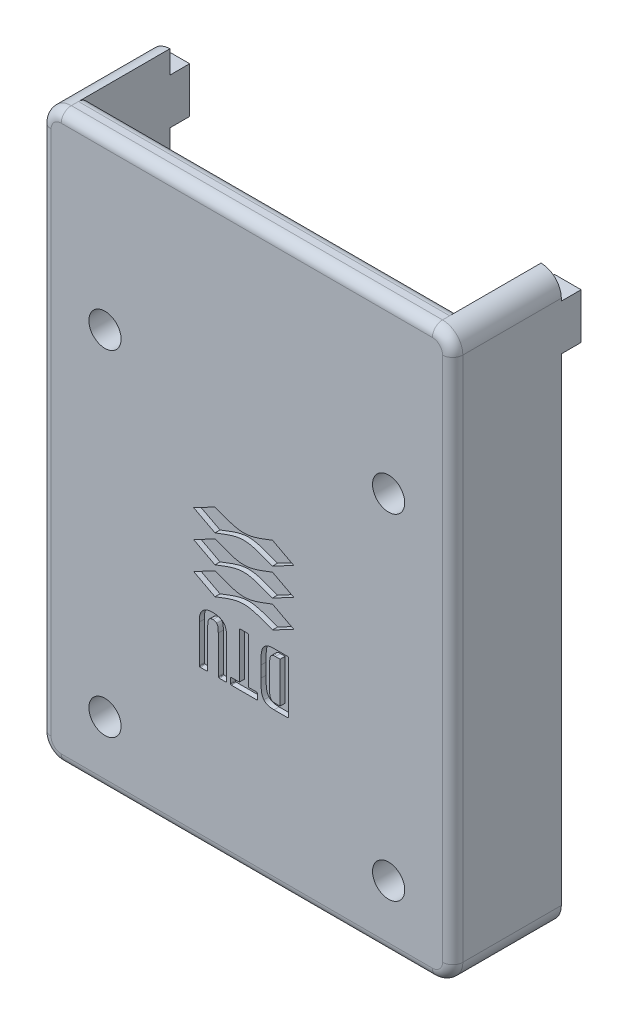
SolidWorks part; units mm, degrees
ref_plane "Front Plane" through (0, 0, 0) normal (0, 0, 1) x (1, 0, 0)
ref_plane "Top Plane" through (0, 0, 0) normal (0, 1, 0) x (1, 0, 0)
ref_plane "Right Plane" through (0, 0, 0) normal (1, 0, 0) x (0, 0, -1)
sketch "Sketch1" plane through (0, 0, 0) normal (0, 0, 1) x (1, 0, 0)
  line L1 (-7.3177, 20.9633) -> (28.2423, 20.9633)
  line L2 (-7.3177, 20.9633) -> (-7.3177, -29.8367)
  line L3 (-7.3177, -29.8367) -> (28.2423, -29.8367)
  line L4 (28.2423, 20.9633) -> (28.2423, -29.8367)
  line L5 (-7.8177, 21.4633) -> (28.7423, 21.4633)
  line L6 (-7.8177, 21.4633) -> (-7.8177, -30.3367)
  line L7 (-7.8177, -30.3367) -> (28.7423, -30.3367)
  line L8 (28.7423, 21.4633) -> (28.7423, -30.3367)
  line L9 (-9.8177, 23.4633) -> (30.7423, 23.4633)
  line L10 (-9.8177, 23.4633) -> (-9.8177, -32.3367)
  line L11 (-9.8177, -32.3367) -> (30.7423, -32.3367)
  line L12 (30.7423, 23.4633) -> (30.7423, -32.3367)
  circle A0 centre (-3.5077, 6.9933) radius 1.5875
  circle A1 centre (24.4323, 6.9933) radius 1.5875
  circle A2 centre (-3.5077, -26.0267) radius 1.5875
  circle A3 centre (24.4323, -26.0267) radius 1.5875
  dimension "D3" = 3.175
  dimension "D4" = 3.175
  dimension "D5" = 3.175
  dimension "D6" = 3.175
  dimension "D1" = 50.8
  dimension "D2" = 35.56
  dimension "D7" = 3.81
  dimension "D8" = 3.81
  dimension "D9" = 3.81
  dimension "D10" = 3.81
  dimension "D11" = 27.94
  dimension "D12" = 33.02
  dimension "D13" = 27.94
  dimension "D14" = 3.81
  dimension "D15" = 0.5
  dimension "D16" = 0.5
  dimension "D17" = 0.5
  dimension "D18" = 0.5
  dimension "D19" = 2
  dimension "D20" = 2
  dimension "D21" = 2
  dimension "D22" = 2
extrude "Boss-Extrude1" add sketch "Sketch1" along normal blind 10.7 contours A1 | A3 | A2 | L9 L12 L11 L10 | A0 region at (24.4323, 6.9933, 0) region at (-3.5077, -26.0267, 0) region at (24.4323, -26.0267, 0)
extrude "Cut-Extrude1" cut sketch "Sketch1<6>" along normal blind 8.7 contours L6 L7 L8 L5
sketch "Sketch1<6>" plane through (0, 0, 0) normal (0, 0, 1) x (1, 0, 0) same geometry as "Sketch1"
sketch "Sketch3" plane through (0, -32.3367, 0) normal (0, -1, 0) x (1, 0, 0)
  line L0 (-9.8177, 0) -> (30.7423, 0) construction
  line L1 (4.1823, 0) -> (16.7423, 0)
  line L2 (4.1823, 0) -> (4.1823, 8)
  line L3 (4.1823, 8) -> (16.7423, 8)
  line L4 (16.7423, 0) -> (16.7423, 8)
  line L5 (30.7423, 10.7) -> (30.7423, 0) construction
  line L6 (-9.8177, 10.7) -> (-9.8177, 0) construction
  dimension "D1" = 8
  dimension "D2" = 14
  dimension "D3" = 14
  dimension "D4" = 12.56
extrude "Cut-Extrude2" cut sketch "Sketch3" against normal blind 5
sketch "Sketch4" plane through (0, 23.4633, 0) normal (0, 1, 0) x (1, 0, 0)
  line L0 (-9.8177, 0) -> (30.7423, 0) construction
  line L1 (-7.8177, 0) -> (28.7423, 0)
  line L2 (-7.8177, 0) -> (-7.8177, -8)
  line L3 (-7.8177, -8) -> (28.7423, -8)
  line L4 (28.7423, 0) -> (28.7423, -8)
  line L5 (-9.8177, -10.7) -> (-9.8177, 0) construction
  line L6 (30.7423, -10.7) -> (30.7423, 0) construction
  dimension "D1" = 8
  dimension "D2" = 2
  dimension "D3" = 2
extrude "Cut-Extrude3" cut sketch "Sketch4" against normal blind 5
sketch "Sketch5" plane through (0, 0, 8.7) normal (0, 0, -1) x (-1, 0, 0)
  line L0 (-24.4323, 9.9933) -> (-28.7423, 9.9933)
  line L1 (-28.7423, 21.4633) -> (-28.7423, -30.3367) construction
  line L2 (-28.7423, 9.9933) -> (-28.7423, 3.9933)
  line L3 (-28.7423, 3.9933) -> (-24.4323, 3.9933)
  line L4 (3.5077, 9.9933) -> (7.8177, 9.9933)
  line L5 (7.8177, 21.4633) -> (7.8177, -30.3367) construction
  line L6 (7.8177, 9.9933) -> (7.8177, 3.9933)
  line L7 (7.8177, 3.9933) -> (3.5077, 3.9933)
  line L8 (3.5077, -22.7267) -> (7.8177, -22.7267)
  line L9 (7.8177, -22.7267) -> (7.8177, -29.3267)
  line L10 (7.8177, 23.4633) -> (7.8177, -30.3367) construction
  line L11 (7.8177, -29.3267) -> (3.5077, -29.3267)
  line L12 (-24.4323, -22.7267) -> (-28.7423, -22.7267)
  line L13 (-28.7423, 23.4633) -> (-28.7423, -30.3367) construction
  line L14 (-28.7423, -22.7267) -> (-28.7423, -29.3267)
  line L15 (-28.7423, -29.3267) -> (-24.4323, -29.3267)
  circle A0 centre (-24.4323, 6.9933) radius 3
  circle A1 centre (3.5077, 6.9933) radius 3
  circle A2 centre (3.5077, -26.0267) radius 3.3
  circle A3 centre (-24.4323, -26.0267) radius 3.3
  circle M2 centre (-24.4323, 6.9933) radius 1.5875
  circle M3 centre (-24.4323, -26.0267) radius 1.5875
  circle M4 centre (3.5077, -26.0267) radius 1.5875
  circle M5 centre (3.5077, 6.9933) radius 1.5875
  line M7 (-28.7423, 21.4633) -> (-28.7423, -30.3367)
  line M9 (7.8177, -30.3367) -> (7.8177, 21.4633)
  dimension "D1" = 6
extrude "Boss-Extrude3" add sketch "Sketch5" along normal blind 8 contours A0 M2 | A1 M5 | A2 M4 | A3 M3 region at (22.371, 9.0546, 8.7) region at (-5.569, 9.0546, 8.7) region at (-5.7752, -23.7593, 8.7) region at (22.1648, -23.7593, 8.7)
extrude "Boss-Extrude4" add sketch "Sketch5<5>" along normal blind 8 contours A0 L0 L3 M7 | A1 L7 L4 M9 | A2 L11 L8 M9 | A3 L12 L15 M7 region at (27.6507, 6.9933, 8.7) region at (26.5873, -22.8056, 8.7) region at (-7.7389, -26.0267, 8.7) region at (-6.7261, 6.9933, 8.7)
sketch "Sketch5<5>" plane through (0, 0, 8.7) normal (0, 0, -1) x (-1, 0, 0) same geometry as "Sketch5"
fillet "Fillet1" radius 2 8 edges at (-9.8177, 23.4633, 5.35) (30.7423, 23.4633, 5.35) (-9.8177, -32.3367, 5.35) (30.7423, -32.3367, 5.35) (4.1823, -31.3367, 0) (16.7423, -31.3367, 0) (16.7423, -31.3367, 8) (4.1823, -31.3367, 8)
fillet "Fillet2" radius 1 9 edges at (-9.2319, 22.8775, 10.7) (-9.8177, -4.4367, 10.7) (-9.2319, -31.7509, 10.7) (10.4623, -32.3367, 10.7) (30.1565, -31.7509, 10.7) (30.7423, -4.4367, 10.7) (30.1565, 22.8775, 10.7) (10.4623, 23.4633, 10.7) (10.4623, 23.4633, 8)
sketch "Sketch6" plane through (0, 0, 0) normal (0, 0, -1) x (-1, 0, 0)
  line L0 (-30.7423, 21.4633) -> (-30.7423, -30.3367) construction
  line L1 (-28.1423, 21.2133) -> (-30.7423, 21.2133)
  line L2 (-28.1423, 21.2133) -> (-28.1423, 16.7133)
  line L3 (-28.1423, 16.7133) -> (-30.7423, 16.7133)
  line L4 (-30.7423, 21.2133) -> (-30.7423, 16.7133)
  line L5 (9.8177, 21.4633) -> (9.8177, -30.3367) construction
  line L6 (7.8177, 21.2133) -> (9.8177, 21.2133)
  line L7 (7.8177, 21.2133) -> (7.8177, 16.7133)
  line L8 (7.8177, 16.7133) -> (9.8177, 16.7133)
  line L9 (9.8177, 21.2133) -> (9.8177, 16.7133)
  line L12 (7.8177, 23.4633) -> (-28.7423, 23.4633) construction
  dimension "D1" = 4.5
  dimension "D2" = 4.5
  dimension "D3" = 2.25
  dimension "D4" = 2.25
extrude "Boss-Extrude5" add sketch "Sketch6" along normal blind 1.95
sketch "Sketch7" plane through (31.1286, 28.3579, 10.7) normal (0, 0, -1) x (1, 0, 0)
  line L0 (-23.8027, 38.7188) -> (-25.9021, 37.616)
  line L1 (-16.0371, 37.616) -> (-18.136, 38.7188)
  line L2 (-18.136, 36.5147) -> (-16.0371, 37.616)
  line L3 (-25.9021, 37.616) -> (-23.8027, 36.5147)
  line L4 (-23.8027, 35.9943) -> (-25.9021, 34.8925)
  line L5 (-16.0371, 34.8925) -> (-18.136, 35.9943)
  line L6 (-18.136, 33.7901) -> (-16.0371, 34.8925)
  line L7 (-25.9021, 34.8925) -> (-23.8027, 33.7901)
  line L8 (-23.8027, 33.2702) -> (-25.9021, 32.1684)
  line L9 (-16.0371, 32.1684) -> (-18.136, 33.2702)
  line L10 (-18.136, 31.0666) -> (-16.0371, 32.1684)
  line L11 (-25.9021, 32.1684) -> (-23.8027, 31.0666)
  line L12 (-17.9818, 45.4573) -> (-16.6721, 45.4573)
  line L13 (-19.2753, 42.2828) -> (-19.2753, 43.4059)
  line L14 (-16.6721, 40.2314) -> (-17.9818, 40.2314)
  line L15 (-16.5624, 45.3476) -> (-16.5624, 40.3411)
  line L16 (-17.3934, 40.8426) -> (-17.3934, 44.8466)
  line L17 (-17.8553, 40.8426) -> (-17.3934, 40.8426)
  line L18 (-18.433, 43.4635) -> (-18.433, 42.2252)
  line L19 (-17.3934, 44.8466) -> (-17.8553, 44.8466)
  line L20 (-25.348, 41.6503) -> (-25.348, 45.3476)
  line L21 (-22.6453, 45.3476) -> (-22.6453, 41.6503)
  line L22 (-23.3666, 45.4573) -> (-22.7549, 45.4573)
  line L23 (-23.4767, 41.6512) -> (-23.4767, 45.3476)
  line L24 (-24.5166, 45.3476) -> (-24.5166, 41.6512)
  line L25 (-25.2384, 45.4573) -> (-24.6262, 45.4573)
  line L26 (-21.3961, 44.797) -> (-21.3961, 40.3411)
  line L27 (-22.1824, 44.797) -> (-21.3961, 44.797)
  line L28 (-22.2923, 45.3476) -> (-22.2923, 44.9066)
  line L29 (-19.7213, 45.4573) -> (-22.1824, 45.4573)
  line L30 (-19.6112, 44.9066) -> (-19.6112, 45.3476)
  line L31 (-20.5074, 44.797) -> (-19.7213, 44.797)
  line L32 (-20.5074, 40.3411) -> (-20.5074, 44.797)
  line L33 (-21.287, 40.2314) -> (-20.617, 40.2314)
  spline S0 degree 3 poles (-18.136, 38.7188) (-20.8551, 37.6612) (-21.0846, 37.6612) (-23.8027, 38.7188) knots 4 4 4 4 5 5 5 5
  spline S1 degree 3 poles (-23.8027, 36.5147) (-21.0846, 37.5719) (-20.8551, 37.5719) (-18.136, 36.5147) knots 1 1 1 1 2 2 2 2
  spline S2 degree 3 poles (-18.136, 35.9943) (-20.8551, 34.9371) (-21.0846, 34.9371) (-23.8027, 35.9943) knots 4 4 4 4 5 5 5 5
  spline S3 degree 3 poles (-23.8027, 33.7901) (-21.0846, 34.8478) (-20.8551, 34.8478) (-18.136, 33.7901) knots 1 1 1 1 2 2 2 2
  spline S4 degree 3 poles (-18.136, 33.2702) (-20.8551, 32.2126) (-21.0846, 32.2126) (-23.8027, 33.2702) knots 4 4 4 4 5 5 5 5
  spline S5 degree 3 poles (-23.8027, 31.0666) (-21.0846, 32.1238) (-20.8551, 32.1238) (-18.136, 31.0666) knots 1 1 1 1 2 2 2 2
  spline S6 degree 3 poles (-18.9888, 45.0981) (-18.8008, 45.3417) (-18.4905, 45.4573) (-17.9818, 45.4573) knots 10 10 10 10 11 11 11 11
  spline S7 degree 3 poles (-19.2753, 43.4059) (-19.2753, 44.229) (-19.2664, 44.7657) (-18.9888, 45.0981) knots 9 9 9 9 10 10 10 10
  spline S8 degree 3 poles (-18.9888, 40.5906) (-19.2664, 40.923) (-19.2753, 41.4598) (-19.2753, 42.2828) knots 7 7 7 7 8 8 8 8
  spline S9 degree 3 poles (-17.9818, 40.2314) (-18.4905, 40.2314) (-18.8008, 40.347) (-18.9888, 40.5906) knots 6 6 6 6 7 7 7 7
  spline S10 degree 3 poles (-16.5912, 40.2607) (-16.6088, 40.2433) (-16.6329, 40.2314) (-16.6721, 40.2314) knots 4 4 4 4 5 5 5 5
  spline S11 degree 3 poles (-16.5624, 40.3411) (-16.5624, 40.3019) (-16.5738, 40.2781) (-16.5912, 40.2607) knots 3 3 3 3 4 4 4 4
  spline S12 degree 3 poles (-16.5912, 45.4285) (-16.5738, 45.4106) (-16.5624, 45.3873) (-16.5624, 45.3476) knots 1 1 1 1 2 2 2 2
  spline S13 degree 3 poles (-16.6721, 45.4573) (-16.6329, 45.4573) (-16.6088, 45.4454) (-16.5912, 45.4285) knots 0 0 0 0 1 1 1 1
  spline S14 degree 3 poles (-18.2752, 40.9885) (-18.1809, 40.8754) (-18.0591, 40.8426) (-17.8553, 40.8426) knots 5 5 5 5 6 6 6 6
  spline S15 degree 3 poles (-18.433, 42.2252) (-18.433, 41.5153) (-18.4206, 41.1631) (-18.2752, 40.9885) knots 4 4 4 4 5 5 5 5
  spline S16 degree 3 poles (-18.2752, 44.7002) (-18.4206, 44.5256) (-18.433, 44.1734) (-18.433, 43.4635) knots 2 2 2 2 3 3 3 3
  spline S17 degree 3 poles (-17.8553, 44.8466) (-18.0591, 44.8466) (-18.1809, 44.8134) (-18.2752, 44.7002) knots 1 1 1 1 2 2 2 2
  spline S18 degree 3 poles (-25.0491, 40.54) (-25.2887, 40.8183) (-25.348, 41.1507) (-25.348, 41.6503) knots 20 20 20 20 21 21 21 21
  spline S19 degree 3 poles (-23.9991, 40.1654) (-24.5138, 40.1654) (-24.8452, 40.3034) (-25.0491, 40.54) knots 19 19 19 19 20 20 20 20
  spline S20 degree 3 poles (-22.9323, 40.5395) (-23.1543, 40.2949) (-23.4904, 40.1654) (-23.9991, 40.1654) knots 18 18 18 18 19 19 19 19
  spline S21 degree 3 poles (-22.6453, 41.6503) (-22.6453, 41.112) (-22.7185, 40.7747) (-22.9323, 40.5395) knots 17 17 17 17 18 18 18 18
  spline S22 degree 3 poles (-22.6746, 45.4285) (-22.6567, 45.4106) (-22.6453, 45.3873) (-22.6453, 45.3476) knots 15 15 15 15 16 16 16 16
  spline S23 degree 3 poles (-22.7549, 45.4573) (-22.7155, 45.4573) (-22.6914, 45.4454) (-22.6746, 45.4285) knots 14 14 14 14 15 15 15 15
  spline S24 degree 3 poles (-23.447, 45.4285) (-23.4301, 45.4454) (-23.406, 45.4573) (-23.3666, 45.4573) knots 12 12 12 12 13 13 13 13
  spline S25 degree 3 poles (-23.4767, 45.3476) (-23.4767, 45.3873) (-23.4646, 45.4106) (-23.447, 45.4285) knots 11 11 11 11 12 12 12 12
  spline S26 degree 3 poles (-23.6313, 40.8997) (-23.5127, 41.0301) (-23.4767, 41.2519) (-23.4767, 41.6512) knots 9 9 9 9 10 10 10 10
  spline S27 degree 3 poles (-23.9885, 40.7598) (-23.8352, 40.7598) (-23.7196, 40.8024) (-23.6313, 40.8997) knots 8 8 8 8 9 9 9 9
  spline S28 degree 3 poles (-24.3623, 40.8987) (-24.2772, 40.8054) (-24.1566, 40.7598) (-23.9885, 40.7598) knots 7 7 7 7 8 8 8 8
  spline S29 degree 3 poles (-24.5166, 41.6512) (-24.5166, 41.2658) (-24.4873, 41.0366) (-24.3623, 40.8987) knots 6 6 6 6 7 7 7 7
  spline S30 degree 3 poles (-24.5458, 45.4285) (-24.5282, 45.4106) (-24.5166, 45.3873) (-24.5166, 45.3476) knots 4 4 4 4 5 5 5 5
  spline S31 degree 3 poles (-24.6262, 45.4573) (-24.587, 45.4573) (-24.5632, 45.4454) (-24.5458, 45.4285) knots 3 3 3 3 4 4 4 4
  spline S32 degree 3 poles (-25.3187, 45.4285) (-25.3016, 45.4454) (-25.2773, 45.4573) (-25.2384, 45.4573) knots 1 1 1 1 2 2 2 2
  spline S33 degree 3 poles (-25.348, 45.3476) (-25.348, 45.3873) (-25.3361, 45.4106) (-25.3187, 45.4285) knots 0 0 0 0 1 1 1 1
  spline S34 degree 3 poles (-22.2635, 44.8258) (-22.2459, 44.8084) (-22.2219, 44.797) (-22.1824, 44.797) knots 17 17 17 17 18 18 18 18
  spline S35 degree 3 poles (-22.2923, 44.9066) (-22.2923, 44.8674) (-22.2802, 44.8431) (-22.2635, 44.8258) knots 16 16 16 16 17 17 17 17
  spline S36 degree 3 poles (-22.2635, 45.4285) (-22.2802, 45.4106) (-22.2923, 45.3873) (-22.2923, 45.3476) knots 14 14 14 14 15 15 15 15
  spline S37 degree 3 poles (-22.1824, 45.4573) (-22.2219, 45.4573) (-22.2459, 45.4454) (-22.2635, 45.4285) knots 13 13 13 13 14 14 14 14
  spline S38 degree 3 poles (-19.6404, 45.4285) (-19.6583, 45.4454) (-19.6819, 45.4573) (-19.7213, 45.4573) knots 11 11 11 11 12 12 12 12
  spline S39 degree 3 poles (-19.6112, 45.3476) (-19.6112, 45.3873) (-19.6231, 45.4106) (-19.6404, 45.4285) knots 10 10 10 10 11 11 11 11
  spline S40 degree 3 poles (-19.6404, 44.8258) (-19.6231, 44.8431) (-19.6112, 44.8674) (-19.6112, 44.9066) knots 8 8 8 8 9 9 9 9
  spline S41 degree 3 poles (-19.7213, 44.797) (-19.6819, 44.797) (-19.6583, 44.8084) (-19.6404, 44.8258) knots 7 7 7 7 8 8 8 8
  spline S42 degree 3 poles (-20.5366, 40.2607) (-20.5188, 40.2781) (-20.5074, 40.3019) (-20.5074, 40.3411) knots 4 4 4 4 5 5 5 5
  spline S43 degree 3 poles (-20.617, 40.2314) (-20.5781, 40.2314) (-20.5538, 40.2433) (-20.5366, 40.2607) knots 3 3 3 3 4 4 4 4
  spline S44 degree 3 poles (-21.3674, 40.2607) (-21.3497, 40.2433) (-21.3259, 40.2314) (-21.287, 40.2314) knots 1 1 1 1 2 2 2 2
  spline S45 degree 3 poles (-21.3961, 40.3411) (-21.3961, 40.3019) (-21.3847, 40.2781) (-21.3674, 40.2607) knots 0 0 0 0 1 1 1 1
extrude "Cut-Extrude5" cut sketch "Sketch7" along normal blind 0.5
